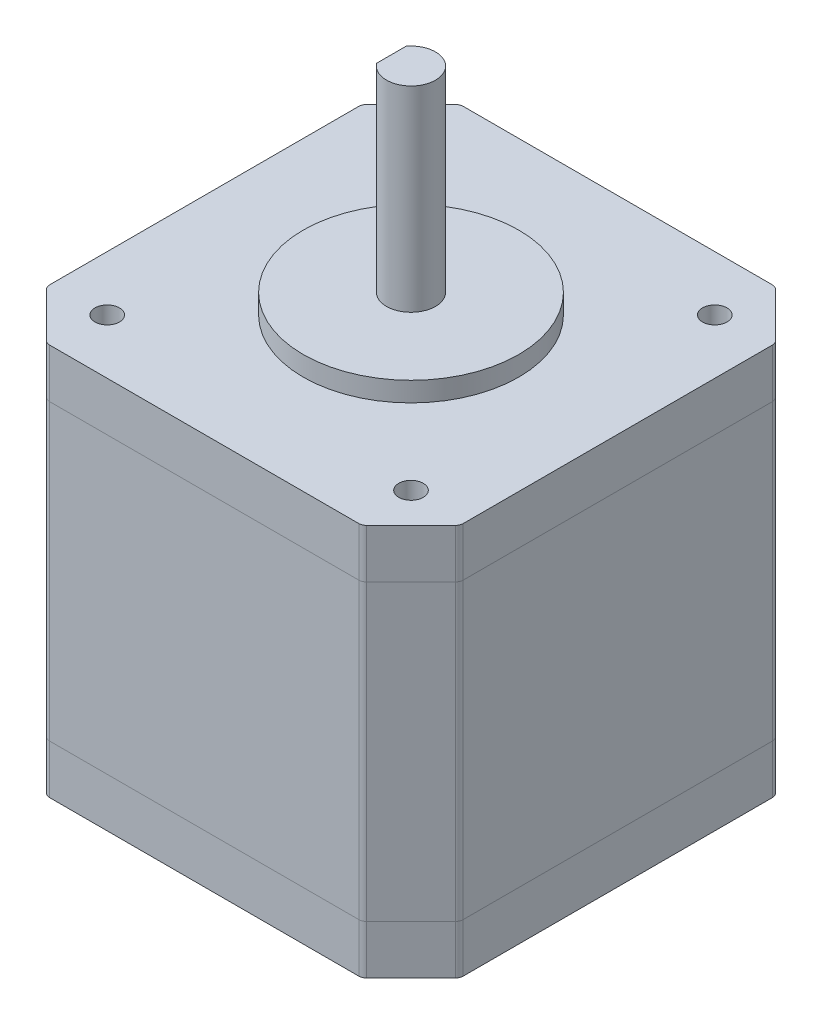
SolidWorks part; units mm, degrees
ref_plane "前视基准面" through (0, 0, 0) normal (0, 0, 1) x (1, 0, 0)
ref_plane "上视基准面" through (0, 0, 0) normal (0, 1, 0) x (1, 0, 0)
ref_plane "右视基准面" through (0, 0, 0) normal (1, 0, 0) x (0, 0, -1)
sketch "草图1" plane through (0, 0, 0) normal (0, 1, 0) x (1, 0, 0)
  line L0 (0, 74.4301) -> (0, -75.3699) construction
  line L1 (-87.211, 0) -> (85.3315, 0) construction
  line L2 (-15.7686, -21.1) -> (15.7686, -21.1)
  line L3 (-21.1, 15.7686) -> (-21.1, -15.7686)
  line L4 (-15.7686, 21.1) -> (15.7686, 21.1)
  line L5 (21.1, 15.7686) -> (21.1, -15.7686)
  line L6 (-15.5, 74.4301) -> (-15.5, -75.3699) construction
  line L7 (-87.211, -15.5) -> (85.3315, -15.5) construction
  line L8 (15.5, 74.4301) -> (15.5, -75.3699) construction
  line L9 (-87.211, 15.5) -> (85.3315, 15.5) construction
  line L10 (-87.211, 21.1) -> (85.3315, 21.1) construction
  line L11 (-21.1, 74.4301) -> (-21.1, -75.3699) construction
  line L12 (-20.8657, 16.3343) -> (-16.3343, 20.8657)
  line L13 (21.1, 74.4301) -> (21.1, -75.3699) construction
  line L14 (16.3343, 20.8657) -> (20.8657, 16.3343)
  line L15 (-87.211, -21.1) -> (85.3315, -21.1) construction
  line L16 (20.8657, -16.3343) -> (16.3343, -20.8657)
  line L17 (-20.8657, -16.3343) -> (-16.3343, -20.8657)
  line L21 (-2, 1.5) -> (-2, -1.5)
  circle A0 centre (-15.5, 15.5) radius 1.25
  circle A1 centre (15.5, 15.5) radius 1.25
  circle A2 centre (15.5, -15.5) radius 1.25
  circle A3 centre (-15.5, -15.5) radius 1.25
  circle A4 centre (0, 0) radius 11
  circle A5 centre (0, 0) radius 2.5
  arc A6 (-21.1, -15.7686) -> (-20.8657, -16.3343) centre (-20.3, -15.7686) ccw
  arc A7 (-16.3343, -20.8657) -> (-15.7686, -21.1) centre (-15.7686, -20.3) ccw
  arc A8 (15.7686, -21.1) -> (16.3343, -20.8657) centre (15.7686, -20.3) ccw
  arc A9 (20.8657, -16.3343) -> (21.1, -15.7686) centre (20.3, -15.7686) ccw
  arc A10 (21.1, 15.7686) -> (20.8657, 16.3343) centre (20.3, 15.7686) ccw
  arc A11 (16.3343, 20.8657) -> (15.7686, 21.1) centre (15.7686, 20.3) ccw
  arc A12 (-15.7686, 21.1) -> (-16.3343, 20.8657) centre (-15.7686, 20.3) ccw
  arc A13 (-20.8657, 16.3343) -> (-21.1, 15.7686) centre (-20.3, 15.7686) ccw
  point P23 (-21.1, 21.1)
  point P26 (21.1, 21.1)
  point P29 (21.1, -21.1)
  point P32 (-21.1, -21.1)
  point P47 (-21.1, -16.1)
  point P51 (-16.1, -21.1)
  point P54 (16.1, -21.1)
  point P57 (21.1, -16.1)
  point P60 (21.1, 16.1)
  point P63 (16.1, 21.1)
  point P66 (-16.1, 21.1)
  point P69 (-21.1, 16.1)
  dimension "D5" = 2.5
  dimension "D11" = 22
  dimension "D12" = 5
  dimension "D14" = 0.8
  dimension "D1" = 21.1
  dimension "D13" = 2
  dimension "D2" = 21.1
  dimension "D3" = 15.5
  dimension "D4" = 15.5
  dimension "D6" = 4
extrude "凸台-拉伸1" add sketch "草图1" along normal blind 40 contours L3 L17 L2 L16 L5 L14 L4 L12 A4 A3 A2 A1 A0 region at (-15.8464, 0, 20.4877)
extrude "切除-拉伸1" cut sketch "草图1<6>" along normal blind 35 contours L3 L17 L2 L16 L5 L14 L4 L12 A4 A3 A2 A1 A0 region at (-15.8464, 0, 20.4877)
sketch "草图1<6>" plane through (0, 0, 0) normal (0, 1, 0) x (1, 0, 0) same geometry as "草图1"
extrude "凸台-拉伸6" add sketch "草图1<7>" along normal blind 35 separate body contours L3 L17 L2 L16 L5 L14 L4 L12 A4 A3 A2 A1 A0 region at (-15.8464, 0, 20.4877)
sketch "草图1<7>" plane through (0, 0, 0) normal (0, 1, 0) x (1, 0, 0) same geometry as "草图1"
extrude "切除-拉伸2" cut sketch "草图1<8>" along normal blind 5 contours L3 L17 L2 L16 L5 L14 L4 L12 A4 A3 A2 A1 A0 region at (-15.8464, 0, 20.4877)
sketch "草图1<8>" plane through (0, 0, 0) normal (0, 1, 0) x (1, 0, 0) same geometry as "草图1"
extrude "凸台-拉伸7" add sketch "草图1<9>" along normal blind 5 separate body contours L3 L17 L2 L16 L5 L14 L4 L12 A4 A3 A2 A1 A0 region at (-15.8464, 0, 20.4877)
sketch "草图1<9>" plane through (0, 0, 0) normal (0, 1, 0) x (1, 0, 0) same geometry as "草图1"
extrude "凸台-拉伸2" add sketch "草图1<3>" along normal blind 42 contours A4 A5 region at (-10.6889, 0, 0)
sketch "草图1<3>" plane through (0, 0, 0) normal (0, 1, 0) x (1, 0, 0) same geometry as "草图1"
extrude "凸台-拉伸3" add sketch "草图1<4>" along normal blind 62 contours L21 A5 region at (0.1209, 0, 0)
sketch "草图1<4>" plane through (0, 0, 0) normal (0, 1, 0) x (1, 0, 0) same geometry as "草图1"
extrude "凸台-拉伸4" add sketch "草图1<5>" along normal blind 47 contours L21 A5 region at (-2.2018, 0, 0)
sketch "草图1<5>" plane through (0, 0, 0) normal (0, 1, 0) x (1, 0, 0) same geometry as "草图1"
sketch "草图2" plane through (0, 0, -21.1) normal (0, 0, -1) x (-1, 0, 0)
  line L0 (-15.7686, 0) -> (15.7686, 0)
  line L1 (-16.1, 6) -> (15.7686, 6)
  line L2 (0, 14.1622) -> (0, -8.6857)
  line L3 (-7, 14.1622) -> (-7, -8.6857)
  line L4 (7, 14.1622) -> (7, -8.6857)
  line L5 (-16.1, 0) -> (15.7686, 0) construction
  point P13 (0, 0)
  point P14 (0, 0)
  point P15 (-15.7686, 0)
  point P18 (15.7686, 0)
  dimension "D1" = 6
  dimension "D2" = 7
  dimension "D3" = 7
extrude "凸台-拉伸5" add sketch "草图2" along normal blind 6 contours L4 L1 L2 L0 | L1 L3 L0 L2 region at (3.5, 3, -21.1) region at (-3.5, 3, -21.1)
fillet "圆角1" radius 1 8 edges at (0, 0, -27.1) (7, 3, -27.1) (0, 6, -27.1) (-7, 3, -27.1) (-7, 0, -24.1) (-7, 6, -24.1) (7, 0, -24.1) (7, 6, -24.1)
